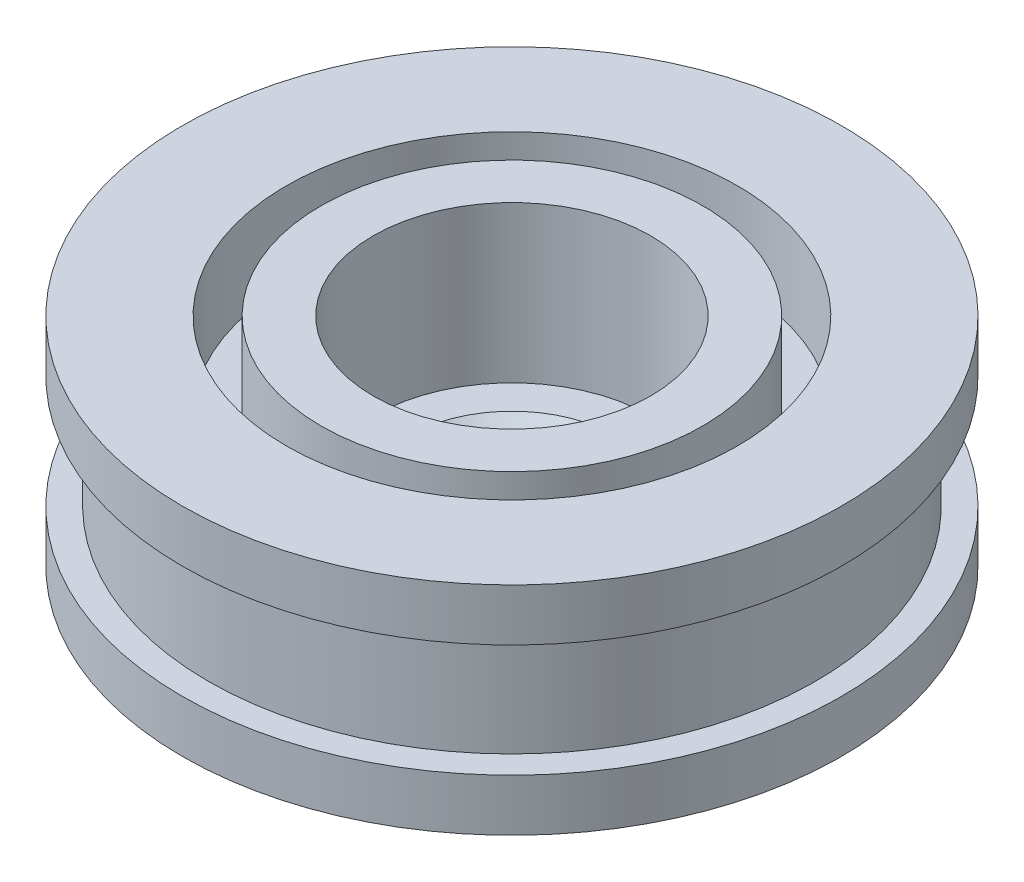
SolidWorks part; units mm, degrees
material "PA Type 6"
ref_plane "Front Plane" through (0, 0, 0) normal (0, 0, 1) x (1, 0, 0)
ref_plane "Top Plane" through (0, 0, 0) normal (0, 1, 0) x (1, 0, 0)
ref_plane "Right Plane" through (0, 0, 0) normal (1, 0, 0) x (0, 0, -1)
sketch "Sketch1" plane through (0, 0, 0) normal (0, 0, 1) x (1, 0, 0)
  line L0 (0, 0) -> (19, 0)
  line L1 (19, 0) -> (19, 3)
  line L2 (19, 3) -> (17.5, 3)
  line L3 (17.5, 3) -> (17.5, 9.5)
  line L4 (17.5, 9.5) -> (19, 9.5)
  line L5 (19, 9.5) -> (19, 12.5)
  line L6 (19, 12.5) -> (0, 12.5)
  line L7 (0, 12.5) -> (0, 0)
  dimension "D1" = 17.5
  dimension "D2" = 3
  dimension "D3" = 1.5
  dimension "D4" = 6.5
revolve "Revolve1" add sketch "Sketch1" angle 360 about L7
sketch "Sketch7" plane through (0, 12.5, 0) normal (0, 1, 0) x (1, 0, 0)
  point P0 (0, 0)
hole_wizard "Ø8.0mm Dowel Hole2" positions "Sketch7" profile "Sketch6" hole size "Ø8.0" standard "DIN" end condition through all
sketch "Sketch6" plane through (0, 12.5, 0) normal (1, 0, 0) x (0, 0, 1)
  line L0 (0, 0) -> (0, 12.5)
  line L1 (0, 12.5) -> (4, 12.5)
  line L2 (4, 12.5) -> (4, 0)
  line L5 (4, 0) -> (0, 0)
  line L11 (0, -6.35) -> (0, 107.95) construction
  dimension "Thru Hole Dia." = 8
  dimension "Thru Hole Depth" = 12.5
sketch "Sketch8" plane through (0, 12.5, 0) normal (0, 1, 0) x (1, 0, 0)
  circle A0 centre (0, 0) radius 8
  dimension "D1" = 16
extrude "Cut-Extrude1" cut sketch "Sketch8" against normal blind 9
chamfer "Chamfer1" distance 2 angle 45 1 edges at (-4, 3.5, 0)
sketch "Sketch9" plane through (0, 12.5, 0) normal (0, 1, 0) x (1, 0, 0)
  circle A0 centre (0, 0) radius 11
  circle A1 centre (0, 0) radius 13
  dimension "D1" = 26
  dimension "D2" = 22
extrude "Cut-Extrude2" cut sketch "Sketch9" against normal blind 5
